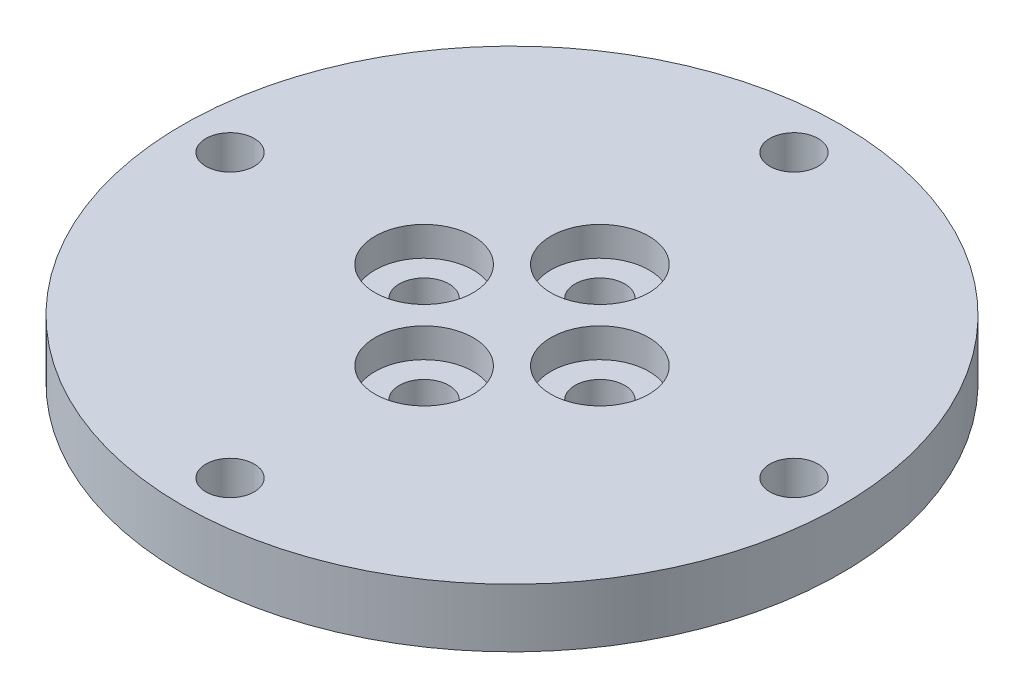
SolidWorks part; units mm, degrees
ref_plane "Спереди" through (0, 0, 0) normal (0, 0, 1) x (1, 0, 0)
ref_plane "Сверху" through (0, 0, 0) normal (0, 1, 0) x (1, 0, 0)
ref_plane "Справа" through (0, 0, 0) normal (1, 0, 0) x (0, 0, -1)
sketch "Эскиз1" plane through (0, 0, 0) normal (0, 1, 0) x (1, 0, 0)
  line L0 (0, 22.5) -> (0, -22.5) construction
  line L1 (22.5, 0) -> (-22.5, 0) construction
  circle A0 centre (0, 0) radius 22.5
  dimension "D1" = 45
extrude "Бобышка-Вытянуть1" add sketch "Эскиз1" along normal blind 4
sketch "Эскиз2" plane through (0, 4, 0) normal (0, 1, 0) x (1, 0, 0)
  circle A0 centre (0, 0) radius 6 construction
  circle A1 centre (0, 0) radius 19.25 construction
  dimension "D1" = 12
  dimension "D2" = 38.5
hole_wizard "Цековка для  винта с полукруглой головкой M31" positions "Эскиз4" profile "Эскиз5" counterbore size "M3" standard "Ansi Metric" end condition through all
sketch "Эскиз4" plane through (0, 4, 0) normal (0, 1, 0) x (1, 0, 0)
  line L0 (0, 22.5) -> (0, -22.5) construction
  line L1 (22.5, 0) -> (-22.5, 0) construction
  circle A0 centre (0, 0) radius 6 construction
  point P0 (0, 6)
  point P6 (-6, 0)
  point P10 (0, -6)
  point P12 (6, 0)
sketch "Эскиз5" plane through (0, 4, -6) normal (1, 0, 0) x (0, 0, 1)
  line L0 (0, 0) -> (0, 4)
  line L1 (0, 4) -> (1.7, 4)
  line L3 (1.7, 4) -> (1.7, 2)
  line L4 (1.7, 2) -> (3.35, 2)
  line L5 (3.35, 2) -> (3.35, 0)
  line L7 (3.35, 0) -> (0, 0)
  line L11 (0, -6.35) -> (0, 107.95) construction
  dimension "Диаметр сквозного отверстия" = 3.4
  dimension "Глубина сквозного отверстия" = 4
  dimension "Диаметр цековки" = 6.7
  dimension "Глубина цековки" = 2
hole_wizard "Отверстие обработанное метчиком M4x0.71" positions "Эскиз7" profile "Эскиз6" tap size "M4x0.7" standard "Ansi Metric" end condition through all
sketch "Эскиз7" plane through (0, 4, 0) normal (0, 1, 0) x (1, 0, 0)
  line L0 (22.5, 0) -> (-22.5, 0) construction
  line L1 (0, 22.5) -> (0, -22.5) construction
  circle A0 centre (0, 0) radius 19.25 construction
  point P0 (-19.25, 0)
  point P6 (0, -19.25)
  point P10 (19.25, 0)
  point P12 (0, 19.25)
sketch "Эскиз6" plane through (-19.25, 4, 0) normal (1, 0, 0) x (0, 0, 1)
  line L0 (0, 0) -> (0, 4)
  line L1 (0, 4) -> (1.65, 4)
  line L2 (1.65, 4) -> (1.65, 0)
  line L5 (1.65, 0) -> (0, 0)
  line L11 (0, -6.35) -> (0, 107.95) construction
  dimension "Диаметр резьбы" = 3.3
  dimension "Глубина проходного сверла" = 4
